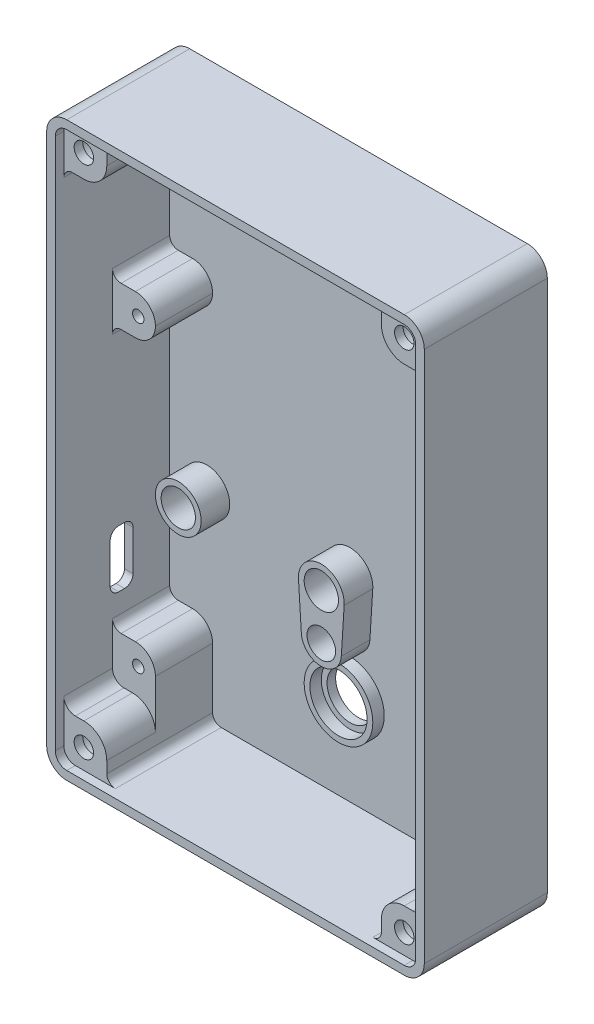
SolidWorks part; units mm, degrees
material "ABS"
ref_plane "Спереди" through (0, 0, 0) normal (0, 0, 1) x (1, 0, 0)
ref_plane "Сверху" through (0, 0, 0) normal (0, 1, 0) x (1, 0, 0)
ref_plane "Справа" through (0, 0, 0) normal (1, 0, 0) x (0, 0, -1)
sketch "Эскиз1" plane through (0, 0, 0) normal (0, 0, 1) x (1, 0, 0)
  line L1 (-33, -50) -> (33, -50)
  line L2 (-33, -50) -> (-33, 50)
  line L3 (-33, 50) -> (33, 50)
  line L4 (33, -50) -> (33, 50)
  line L5 (-33, -50) -> (33, 50) construction
  line L6 (-33, 50) -> (33, -50) construction
  line L7 (-31.5, -48.5) -> (31.5, -48.5)
  line L8 (-31.5, -48.5) -> (-31.5, 48.5)
  line L9 (-31.5, 48.5) -> (31.5, 48.5)
  line L10 (31.5, -48.5) -> (31.5, 48.5)
  line L11 (-31.5, -48.5) -> (31.5, 48.5) construction
  line L12 (-31.5, 48.5) -> (31.5, -48.5) construction
  point P0 (0, 0)
  point P6 (0, 0)
  dimension "D1" = 66
  dimension "D2" = 100
  dimension "D3" = 1.5
  dimension "D4" = 1.5
extrude "Бобышка-Вытянуть1" add sketch "Эскиз1" along normal blind 20
sketch "Эскиз3" plane through (0, 0, 0) normal (0, 0, -1) x (-1, 0, 0)
  line L1 (-33, 50) -> (33, 50)
  line L2 (-33, 50) -> (-33, -50)
  line L3 (-33, -50) -> (33, -50)
  line L4 (33, 50) -> (33, -50)
extrude "Бобышка-Вытянуть2" add sketch "Эскиз3" along normal blind 1.5
sketch "Эскиз4" plane through (0, 0, 0) normal (0, 0, 1) x (1, 0, 0)
  line L0 (-31.5, 48.5) -> (-31.5, -48.5) construction
  line L1 (-31.5, 20) -> (-24, 20)
  line L2 (-31.5, 20) -> (-31.5, 13)
  line L3 (-31.5, 13) -> (-24, 13)
  line L4 (-24, 20) -> (-24, 13)
  line L5 (31.5, -48.5) -> (31.5, 48.5) construction
  line L6 (31.5, 20) -> (24, 20)
  line L7 (31.5, 20) -> (31.5, 13)
  line L8 (31.5, 13) -> (24, 13)
  line L9 (24, 20) -> (24, 13)
  line L10 (-31.5, -48.5) -> (31.5, -48.5) construction
  line L11 (-31.5, -41) -> (-24, -41)
  line L12 (-31.5, -41) -> (-31.5, -33)
  line L13 (-31.5, -33) -> (-24, -33)
  line L14 (-24, -41) -> (-24, -33)
  line L15 (31.5, -41) -> (24, -41)
  line L16 (31.5, -41) -> (31.5, -33)
  line L17 (31.5, -33) -> (24, -33)
  line L18 (24, -41) -> (24, -33)
  line L19 (31.5, -48.5) -> (31.5, 48.5) construction
  dimension "D1" = 7.5
  dimension "D2" = 8
  dimension "D3" = 7
  dimension "D4" = 46
  dimension "D5" = 7.5
extrude "Бобышка-Вытянуть3" add sketch "Эскиз4" along normal blind 10
sketch "Эскиз5" plane through (0, 0, 10) normal (0, 0, 1) x (1, 0, 0)
  line L1 (-24, -41) -> (-24, -33) construction
  line L2 (-24, 13) -> (-24, 20) construction
  circle A0 centre (-27, 16.5) radius 1
  circle A1 centre (27, 16.5) radius 1
  circle A2 centre (-27, -36.5) radius 1
  circle A3 centre (27, -36.5) radius 1
  point P10 (-24, 16.5)
  point P13 (-27, -36.5)
  dimension "D5" = 2
  dimension "D6" = 53
  dimension "D1" = 54
  dimension "D2" = 3
sketch "Эскиз8" plane through (0, 0, 0) normal (0, 0, 1) x (1, 0, 0)
  line L0 (-24, -41) -> (-24, -33) construction
  line L1 (-31.5, 48.5) -> (-24, 48.5)
  line L2 (-31.5, 48.5) -> (-31.5, 41)
  line L3 (-31.5, 41) -> (-24, 41)
  line L4 (-24, 48.5) -> (-24, 41)
  line L5 (31.5, 48.5) -> (24, 48.5)
  line L6 (31.5, 48.5) -> (31.5, 41)
  line L7 (31.5, 41) -> (24, 41)
  line L8 (24, 48.5) -> (24, 41)
  line L9 (31.5, -48.5) -> (24, -48.5)
  line L10 (31.5, -48.5) -> (31.5, -41)
  line L11 (31.5, -41) -> (24, -41)
  line L12 (24, -48.5) -> (24, -41)
  line L13 (-31.5, -48.5) -> (-24, -48.5)
  line L14 (-31.5, -48.5) -> (-31.5, -41)
  line L15 (-31.5, -41) -> (-24, -41)
  line L16 (-24, -48.5) -> (-24, -41)
  line L18 (24, -33) -> (24, -41) construction
  line L19 (-24, 20) -> (-31.5, 20) construction
  line L21 (-31.5, -41) -> (-24, -41) construction
extrude "Бобышка-Вытянуть4" add sketch "Эскиз8" along normal blind 18.5
fillet "Скругление1" radius 1.5 12 edges at (-31.5, -33, 5) (-24, -48.5, 9.25) (24, -48.5, 9.25) (31.5, -33, 5) (31.5, 13, 5) (31.5, 20, 5) (-31.5, 13, 5) (-31.5, 20, 5) (-31.5, 41, 9.25) (-24, 48.5, 9.25) (31.5, 41, 9.25) (24, 48.5, 9.25)
fillet "Скругление3" radius 2 6 edges at (-31.5, -48.5, 19.25) (-31.5, -41, 14.25) (31.5, -48.5, 19.25) (31.5, -41, 14.25) (-31.5, 48.5, 19.25) (31.5, 48.5, 19.25)
fillet "Скругление4" radius 3.5 4 edges at (-33, -50, 9.25) (33, -50, 9.25) (33, 50, 9.25) (-33, 50, 9.25)
sketch "Эскиз9" plane through (0, 0, 0) normal (0, 0, 1) x (1, 0, 0)
  circle A0 centre (-25, -14) radius 3
  circle A1 centre (25, -14) radius 3
  circle A2 centre (0, -22) radius 2.5
  circle A3 centre (0, -14) radius 3
  circle A4 centre (0, -32.5) radius 4
  dimension "D1" = 6
  dimension "D6" = 8
  dimension "D8" = 5
  dimension "D2" = 8
  dimension "D3" = 10.5
  dimension "D4" = 25
  dimension "D5" = 25
  dimension "D7" = 4
extrude "Вырез-Вытянуть1" cut sketch "Эскиз9" against normal through all
sketch "Эскиз10" plane through (0, 0, 0) normal (0, 0, 1) x (1, 0, 0)
  line L0 (3.9922, -14.25) -> (3.4932, -22.2188)
  line L1 (-3.9922, -14.25) -> (-3.4932, -22.2188)
  circle A0 centre (-25, -14) radius 3
  circle A1 centre (0, -22) radius 2.5 construction
  circle A2 centre (0, -14) radius 3
  circle A3 centre (25, -14) radius 3
  circle A4 centre (0, -22) radius 2.5
  circle A5 centre (-25, -14) radius 3 construction
  circle A6 centre (0, -14) radius 4
  circle A7 centre (25, -14) radius 4
  circle A9 centre (-25, -14) radius 4
  arc A12 (-3.4932, -22.2188) -> (3.4932, -22.2188) centre (0, -22) ccw
  circle M1 centre (-25, -14) radius 3
  circle M2 centre (0, -14) radius 3
  circle M3 centre (0, -22) radius 2.5
  circle M4 centre (25, -14) radius 3
  dimension "D1" = 1
  dimension "D2" = 1
extrude "Бобышка-Вытянуть5" add sketch "Эскиз10" along normal blind 5 contours L1 A12 L0 A6 M3 | A6 M2 | A7 M4 | A9 M1 region at (3.605, -18.2258, 0) region at (0, -17.8869, 0) region at (21.1131, -14, 0) region at (-28.8869, -14, 0)
sketch "Эскиз11" plane through (0, 0, -1.5) normal (0, 0, -1) x (-1, 0, 0)
  line L0 (29.5, 50) -> (-29.5, 50) construction
  line L1 (33, -46.5) -> (33, 46.5) construction
  line L2 (-29.5, -50) -> (29.5, -50) construction
  line L3 (-33, 46.5) -> (-33, -46.5) construction
  circle A0 centre (-28, 45) radius 3
  circle A1 centre (28, 45) radius 3
  circle A2 centre (28, -45) radius 3
  circle A3 centre (-28, -45) radius 3
  dimension "D2" = 6
  dimension "D1" = 5
  dimension "D3" = 5
  dimension "D4" = 5
  dimension "D5" = 5
extrude "Вырез-Вытянуть2" cut sketch "Эскиз11" against normal blind 18.5
sketch "Эскиз12" plane through (0, 0, 17) normal (0, 0, -1) x (-1, 0, 0)
  point P0 (-28, 45)
  point P1 (28, 45)
  point P3 (28, -45)
  point P5 (-28, -45)
hole_wizard "Отверстие с зазором M31" positions "Эскиз13" profile "Эскиз14" hole size "M3" standard "DIN" end condition through all
sketch "Эскиз13" plane through (0, 0, 17) normal (0, 0, -1) x (-1, 0, 0)
  point P0 (-28, 45)
  point P3 (28, 45)
  point P6 (28, -45)
  point P9 (-28, -45)
sketch "Эскиз14" plane through (28, 45, 17) normal (1, 0, 0) x (0, 1, 0)
  line L0 (0, 0) -> (0, 3)
  line L1 (0, 3) -> (1.7, 3)
  line L2 (1.7, 3) -> (1.7, 0)
  line L5 (1.7, 0) -> (0, 0)
  line L11 (0, -6.35) -> (0, 107.95) construction
  dimension "Диаметр сквозного отверстия" = 3.4
  dimension "Глубина сквозного отверстия" = 3
extrude "Вырез-Вытянуть4" cut sketch "Эскиз5" against normal blind 4
sketch "Эскиз15" plane through (-31.5, 0, 0) normal (-1, 0, 0) x (0, 0, 1)
  line L1 (6.4, -28) -> (10.4, -28)
  line L2 (6.4, -28) -> (6.4, -18)
  line L3 (6.4, -18) -> (10.4, -18)
  line L4 (10.4, -28) -> (10.4, -18)
  line L5 (10, -39) -> (10, -31.5) construction
  dimension "D1" = 4
  dimension "D2" = 10
  dimension "D3" = 8.5
  dimension "D4" = 0.4
extrude "Вырез-Вытянуть3" cut sketch "Эскиз15" along normal up to surface (1.5 mm away) up to face at (-33, 0, 9.25)
fillet "Скругление5" radius 1.5 4 edges at (-32.25, -28, 10.4) (-32.25, -18, 10.4) (-32.25, -18, 6.4) (-32.25, -28, 6.4)
sketch "Эскиз16" plane through (0, 0, 0) normal (0, 0, 1) x (1, 0, 0)
  circle A0 centre (0, -32.5) radius 5
  circle A1 centre (0, -32.5) radius 6
  dimension "D1" = 1
  dimension "D2" = 10
extrude "Бобышка-Вытянуть6" add sketch "Эскиз16" along normal blind 2
fillet "Скругление6" radius 3.5 6 edges at (24, -33, 5) (-24, -33, 5) (24, 13, 5) (24, 20, 5) (-24, 13, 5) (-24, 20, 5)
fillet "Скругление7" radius 4 4 edges at (24, 41, 9.25) (-24, -41, 14.25) (24, -41, 14.25) (-24, 41, 9.25)
